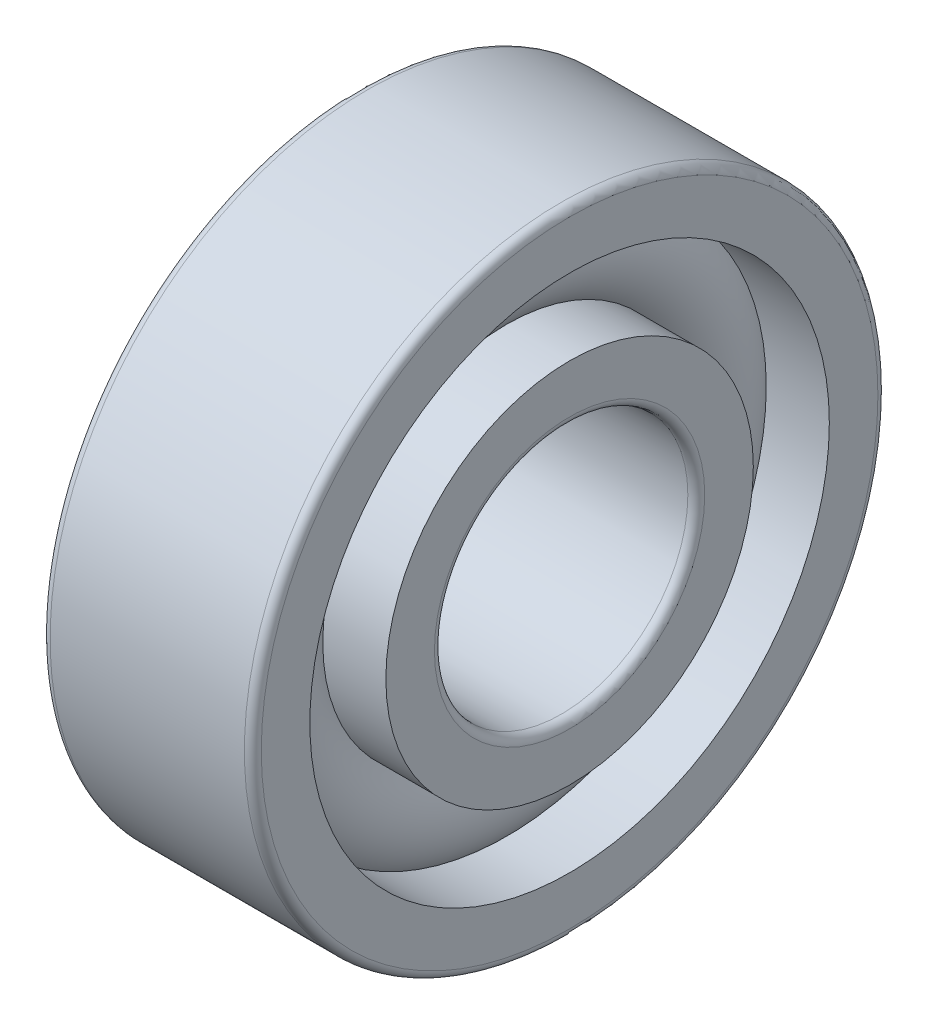
SolidWorks part; units mm, degrees
ref_plane "Plane1" through (0, 0, 0) normal (0, 0, 1) x (1, 0, 0)
ref_plane "Plane2" through (0, 0, 0) normal (0, 1, 0) x (1, 0, 0)
ref_plane "Plane3" through (0, 0, 0) normal (1, 0, 0) x (0, 0, -1)
sketch "Clipboard" plane through (0, 0, 0) normal (0, 0, 1) x (1, 0, 0)
  line L0 (-10, 0) -> (10, 0) construction
  line L1 (0, 0) -> (22.3471, -0.7804)
  line L2 (0, 0) -> (5.2468, 0.1832)
  line L3 (0, 0) -> (22.3471, -0.7804)
  line L4 (0, 0) -> (-22.3573, -0.3902)
  dimension "BallCLRad" = 5.25
  dimension "Count" = 2
  dimension "Show_count" = 2
  dimension "Max_count" = 2
  dimension "Min_count" = 1
sketch "CagSpiSke" plane through (0, 0, 0) normal (0, 0, 1) x (1, 0, 0)
  line L0 (0.135, 5.025) -> (0.135, 5.475)
  line L1 (0.135, 5.475) -> (-0.135, 5.475)
  line L2 (-0.135, 5.475) -> (-0.135, 5.025)
  line L3 (-0.135, 5.025) -> (0.135, 5.025)
  line L4 (-20.6375, 0) -> (20.6375, 0) construction
  line L5 (0, 0) -> (0, 23.7692) construction
  dimension "Thickness" = 0.27
  dimension "OD" = 10.95
  dimension "ID" = 10.05
revolve "CageSpine" add sketch "CagSpiSke" angle 0.001 about L4
ref_axis "Axis1" through (-50, 0, 0) along (1, 0, 0)
sketch "CagBalSke" plane through (0, 0, 0) normal (0, 0, 1) x (1, 0, 0)
  line L0 (-1.485, 5.25) -> (1.485, 5.25)
  line L1 (-1.905, 5.25) -> (1.905, 5.25) construction
  line L2 (-10, 0) -> (10, 0) construction
  line L3 (0, 0) -> (0, 24) construction
  arc A0 (1.485, 5.25) -> (-1.485, 5.25) centre (0, 5.25) cw
  dimension "CageWallOD" = 2.97
  dimension "BallCLRad" = 5.25
revolve "CageBall" [suppressed] add sketch "CagBalSke" angle 360 about L1 reverse direction yes
pattern_circular "CageBalls" [suppressed] count 2 every 180 about axis through (-50, 0, 0) along (1, 0, 0)
sketch "CagTrmODSke" plane through (0, 0, 0) normal (0, 0, 1) x (1, 0, 0)
  line L0 (1.486, 5.475) -> (1.486, 6.736)
  line L1 (1.486, 6.736) -> (-1.486, 6.736)
  line L2 (-1.486, 6.736) -> (-1.486, 5.475)
  line L3 (-1.486, 5.475) -> (1.486, 5.475)
  line L4 (-20.6375, 0) -> (20.6375, 0) construction
  line L5 (0, 0) -> (0, 25) construction
  dimension "Width" = 2.972
  dimension "ID" = 10.95
  dimension "OD" = 13.472
revolve "CageTrimOD" [suppressed] cut sketch "CagTrmODSke" angle 360 about L4 reverse direction yes
sketch "CagTrmIDSke" plane through (0, 0, 0) normal (0, 0, 1) x (1, 0, 0)
  line L0 (1.486, 3.766) -> (1.486, 5.025)
  line L1 (1.486, 5.025) -> (-1.486, 5.025)
  line L2 (-1.486, 5.025) -> (-1.486, 3.766)
  line L3 (-1.486, 3.766) -> (1.486, 3.766)
  line L4 (-20.6375, 0) -> (20.6375, 0) construction
  line L5 (0, 0) -> (0, 25) construction
  dimension "ID" = 7.532
  dimension "OD" = 10.05
  dimension "Width" = 2.972
revolve "CageTrimID" [suppressed] cut sketch "CagTrmIDSke" angle 360 about L4 reverse direction yes
sketch "BalSimSke" plane through (0, 0, 0) normal (0, 0, 1) x (1, 0, 0)
  line L0 (-10, 0) -> (10, 0) construction
  line L1 (-10, 5.25) -> (10, 5.25) construction
  line L2 (0, 0) -> (0, 23) construction
  circle A0 centre (0, 5.25) radius 1.35
  dimension "Ball_diameter" = 2.7
  dimension "BallCLRad" = 5.25
revolve "BallsSimplified" add sketch "BalSimSke" angle 360 about L0
sketch "BalDetSke" plane through (0, 0, 0) normal (0, 0, 1) x (1, 0, 0)
  line L0 (-1.35, 5.25) -> (1.35, 5.25)
  line L1 (-1.905, 5.25) -> (1.905, 5.25) construction
  line L2 (0, 0) -> (0, 25) construction
  arc A0 (1.35, 5.25) -> (-1.35, 5.25) centre (0, 5.25) cw
  dimension "Ball_diameter" = 2.7
  dimension "BallCLRad" = 5.25
revolve "BallDetailed" [suppressed] add sketch "BalDetSke" angle 360 about L1 reverse direction yes
sketch "InnRacSke" plane through (0, 0, 0) normal (0, 0, 1) x (1, 0, 0)
  line L0 (-0.9724, 4.35) -> (-2.5, 4.35)
  line L1 (-2.5, 4.35) -> (-2.5, 3.2)
  line L2 (-2.3, 3) -> (2.3, 3)
  line L3 (2.5, 3.2) -> (2.5, 4.35)
  line L4 (2.5, 4.35) -> (0.9724, 4.35)
  line L5 (-20.6375, 0) -> (20.6375, 0) construction
  line L6 (0, 0) -> (0, 30) construction
  arc A0 (-2.5, 3.2) -> (-2.3, 3) centre (-2.3, 3.2) ccw
  arc A1 (2.3, 3) -> (2.5, 3.2) centre (2.3, 3.2) ccw
  arc A2 (0.9724, 4.35) -> (-0.9724, 4.35) centre (0, 5.25) cw
  dimension "Fillet_radius" = 0.2
  dimension "Ball_diameter" = 2.65
  dimension "ID" = 6
  dimension "OD" = 8.7
  dimension "Width" = 5
  dimension "BallCLRad" = 5.25
revolve "InnerRace" add sketch "InnRacSke" angle 360 about L5 reverse direction yes
sketch "OutRacSke" plane through (0, 0, 0) normal (0, 0, 1) x (1, 0, 0)
  line L0 (-0.9724, 6.15) -> (-2.5, 6.15)
  line L1 (-2.5, 6.15) -> (-2.5, 7.3)
  line L2 (-2.3, 7.5) -> (2.3, 7.5)
  line L3 (2.5, 7.3) -> (2.5, 6.15)
  line L4 (2.5, 6.15) -> (0.9724, 6.15)
  line L5 (-20.6375, 0) -> (20.6375, 0) construction
  line L6 (0, 0) -> (0, 30) construction
  arc A0 (-2.5, 7.3) -> (-2.3, 7.5) centre (-2.3, 7.3) cw
  arc A1 (2.3, 7.5) -> (2.5, 7.3) centre (2.3, 7.3) cw
  arc A2 (0.9724, 6.15) -> (-0.9724, 6.15) centre (0, 5.25) ccw
  dimension "Fillet_radius" = 0.2
  dimension "Ball_diameter" = 2.65
  dimension "OD" = 15
  dimension "ID" = 12.3
  dimension "Width" = 5
  dimension "BallCLRad" = 5.25
revolve "OuterRace" add sketch "OutRacSke" angle 360 about L5 reverse direction yes
pattern_circular "BallsDetailed" [suppressed] count 2 every 180 about axis through (-50, 0, 0) along (1, 0, 0)
equation "\"BallCLRad@Clipboard\" = ( \"OD@OutRacSke\" + \"ID@InnRacSke\" ) / 4"
equation "\"BallCLRad@BalSimSke\" = \"BallCLRad@Clipboard\""
equation "\"BallCLRad@BalDetSke\" = \"BallCLRad@Clipboard\""
equation "\"BallCLRad@InnRacSke\" = \"BallCLRad@Clipboard\""
equation "\"BallCLRad@OutRacSke\" = \"BallCLRad@Clipboard\""
equation "\"Ball_diameter@InnRacSke\" = \"Ball_diameter@BalDetSke\" - 0.05"
equation "\"Ball_diameter@OutRacSke\" = \"Ball_diameter@BalDetSke\" - 0.05"
equation "\"Ball_diameter@BalSimSke\" = \"Ball_diameter@BalDetSke\""
equation "\"Width@OutRacSke\" = \"Width@InnRacSke\""
equation "\"Fillet_radius@OutRacSke\" = \"Fillet_radius@InnRacSke\""
equation "\"Max_count@Clipboard\" = int( 3.14159265 / atn(( \"Ball_diameter@BalDetSke\" / 2) / sqr( \"BallCLRad@Clipboard\"  *  \"BallCLRad@Clipboard\" - ( \"Ball_diameter@BalDetSke\" / 2) *  ( \"Ball_diameter@BalDetSke\" / 2))))"
equation "\"Max_count@Clipboard\" = ((sgn( \"Max_count@Clipboard\" - \"Count@Clipboard\" )-1)*( \"Max_count@Clipboard\" - \"Count@Clipboard\" ))/-2+ \"Count@Clipboard\""
equation "\"Count@BallsDetailed\" = int( \"Show_count@Clipboard\" ) "
equation "\"Count@BallsDetailed\" = ((sgn( \"Count@BallsDetailed\" - \"Max_count@Clipboard\" )-1)*( \"Count@BallsDetailed\" - \"Max_count@Clipboard\" ))/-2+ \"Max_count@Clipboard\""
equation "\"Count@BallsDetailed\" = ((sgn( \"Count@BallsDetailed\" - \"Min_count@Clipboard\" )+1)*( \"Count@BallsDetailed\" - \"Min_count@Clipboard\"))/2 +\"Min_count@Clipboard\""
equation "\"Angle@BallsDetailed\" = 360.0 / \"Max_count@Clipboard\""
equation "\"BallCLRad@CagBalSke\" = \"BallCLRad@Clipboard\""
equation "\"Count@CageBalls\" = \"Count@BallsDetailed\""
equation "\"Angle@CageBalls\" = \"Angle@BallsDetailed\""
equation "\"Angle@CageSpine\" =  \"Angle@CageBalls\" * ( \"Count@CageBalls\" -1 + int( \"Count@CageBalls\" / \"Max_count@Clipboard\" ) )  + 0.001 -  int( \"Count@CageBalls\" / \"Max_count@Clipboard\" ) * 0.001"
equation "\"Angle@CageSpine\" =  \"Angle@CageSpine\" * int( \"Min_count@Clipboard\" / 2) + int(1 / \"Min_count@Clipboard\")  * 0.001"
equation "\"CageWallOD@CagBalSke\" =  \"Ball_diameter@BalDetSke\" * 1.1"
equation "\"Thickness@CagSpiSke\" =  \"Ball_diameter@BalDetSke\" * 0.1"
equation "\"OD@CagTrmODSke\" = \"BallCLRad@Clipboard\" * 2 + \"CageWallOD@CagBalSke\" + 0.002"
equation "\"ID@CagTrmODSke\" = \"BallCLRad@Clipboard\" * 2 + \"Ball_diameter@BalDetSke\" / 6"
equation "\"OD@CagTrmIDSke\" = \"BallCLRad@Clipboard\" * 2 - \"Ball_diameter@BalDetSke\" / 6"
equation "\"ID@CagTrmIDSke\" = \"BallCLRad@Clipboard\" * 2 - \"CageWallOD@CagBalSke\" + 0.002"
equation "\"OD@CagSpiSke\" = \"ID@CagTrmODSke\""
equation "\"ID@CagSpiSke\" = \"OD@CagTrmIDSke\""
equation "\"Width@CagTrmODSke\" = \"CageWallOD@CagBalSke\" + 0.002"
equation "\"Width@CagTrmIDSke\" = \"CageWallOD@CagBalSke\" + 0.002"
